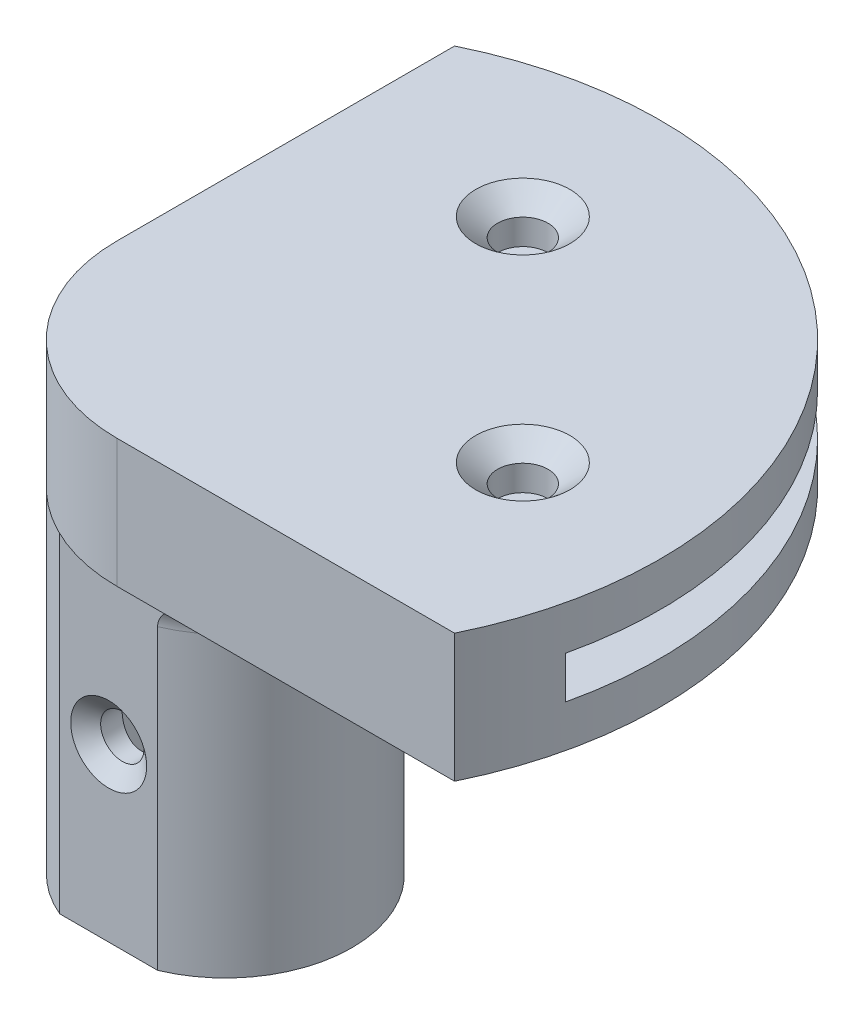
SolidWorks part; units mm, degrees
material "ABS"
ref_plane "Front Plane" through (0, 0, 0) normal (0, 0, 1) x (1, 0, 0)
ref_plane "Top Plane" through (0, 0, 0) normal (0, 1, 0) x (1, 0, 0)
ref_plane "Right Plane" through (0, 0, 0) normal (1, 0, 0) x (0, 0, -1)
sketch "Sketch2" plane through (0, 0, 0) normal (0, 1, 0) x (1, 0, 0)
  line L0 (-6.1346, -10.9507) -> (1.2352, -10.9507)
  line L1 (-6.1346, 6.6161) -> (1.2352, 6.6161)
  arc A0 (-6.1346, 6.6161) -> (-6.1346, -10.9507) centre (-2.4496, -2.1673) ccw
  circle A1 centre (-2.4496, -2.1673) radius 6.35
  arc A2 (1.2352, -10.9507) -> (1.2352, 6.6161) centre (-2.4496, -2.1673) ccw
  point P0 (-11.9404, -2.9741)
  point P1 (-9.7575, -8.2765)
  dimension "D1" = 12.7
sketch "Sketch3" plane through (0, 0, 0) normal (0, 1, 0) x (1, 0, 0)
  line L0 (0.0818, -12.8507) -> (25.4818, -12.8507)
  line L1 (-12.7876, 0.0187) -> (-12.7876, 25.4187)
  line L2 (-6.6277, -6.6908) -> (-6.6277, 27.5993)
  line L3 (-6.6277, -6.6908) -> (27.6625, -6.6908)
  line L4 (20.0088, 19.9456) -> (-9.0182, -9.0814) construction
  arc A0 (-12.7876, 0.0187) -> (0.0818, -12.8507) centre (0.0818, 0.0187) ccw
  arc A1 (25.4818, -12.8507) -> (-12.7876, 25.4187) centre (-0.2222, -0.2854) ccw
  point P0 (-9.0182, -9.0814)
  point P2 (20.0088, 19.9456)
  point P17 (-10.1818, -7.7452)
  dimension "D1" = 6.1599
extrude "Boss-Extrude1" add sketch "Sketch3" along normal blind 3.175 contours L0 A1 L1 A0
sketch "Sketch5" plane through (0, 3.175, 0) normal (0, 1, 0) x (1, 0, 0)
  line L0 (-6.6277, -6.6908) -> (-6.6277, 27.5993) construction
  line L1 (-6.6277, -6.6908) -> (27.6625, -6.6908) construction
  line L2 (0.0818, -12.8507) -> (25.4818, -12.8507)
  line L3 (-12.7876, 25.4187) -> (-12.7876, 0.0187)
  line L4 (0.0818, -12.8507) -> (25.4818, -12.8507)
  line L5 (-12.7876, 25.4187) -> (-12.7876, 0.0187)
  line L6 (-6.6277, -6.6908) -> (-6.6277, 27.5993)
  line L7 (-6.6277, -6.6908) -> (27.6625, -6.6908)
  arc A2 (25.4818, -12.8507) -> (-12.7876, 25.4187) centre (-0.2222, -0.2854) ccw
  arc A3 (-12.7876, 0.0187) -> (0.0818, -12.8507) centre (0.0818, 0.0187) ccw
  arc A4 (25.4818, -12.8507) -> (-12.7876, 25.4187) centre (-0.2222, -0.2854) ccw
  arc A5 (-12.7876, 0.0187) -> (0.0818, -12.8507) centre (0.0818, 0.0187) ccw
  dimension "D1" = 0
extrude "Boss-Extrude2" add sketch "Sketch5" along normal blind 3.175 contours L5 A5 L4 A4 L7 L6
ref_plane "Plane3" through (0, 6.35, 0) normal (0, 1, 0) x (1, 0, 0)
sketch "Sketch6" plane through (0, 6.35, 0) normal (0, 1, 0) x (1, 0, 0)
  line L0 (-12.7876, 25.4187) -> (-12.7876, 0.0187) construction
  line L1 (0.0818, -12.8507) -> (25.4818, -12.8507) construction
  line L2 (-12.7876, 25.4187) -> (-12.7876, 0.0187)
  line L3 (0.0818, -12.8507) -> (25.4818, -12.8507)
  arc A0 (-6.6277, 27.5993) -> (-12.7876, 25.4187) centre (-0.2222, -0.2854) ccw construction
  arc A1 (27.6625, -6.6908) -> (-6.6277, 27.5993) centre (-0.2222, -0.2854) ccw construction
  arc A2 (-12.7876, 0.0187) -> (0.0818, -12.8507) centre (0.0818, 0.0187) ccw construction
  arc A3 (25.4818, -12.8507) -> (27.6625, -6.6908) centre (-0.2222, -0.2854) ccw construction
  arc A4 (-6.6277, 27.5993) -> (-12.7876, 25.4187) centre (-0.2222, -0.2854) ccw
  arc A5 (27.6625, -6.6908) -> (-6.6277, 27.5993) centre (-0.2222, -0.2854) ccw
  arc A6 (-12.7876, 0.0187) -> (0.0818, -12.8507) centre (0.0818, 0.0187) ccw
  arc A7 (25.4818, -12.8507) -> (27.6625, -6.6908) centre (-0.2222, -0.2854) ccw
extrude "Boss-Extrude3" add sketch "Sketch6" along normal blind 3.302
extrude "Boss-Extrude4" add sketch "Sketch2" against normal blind 25.4
sketch "Sketch28" plane through (0, 0, 0) normal (0, -1, 0) x (-1, 0, 0)
  arc A0 (9.7575, -8.2765) -> (12.7876, 0.0187) centre (-0.0818, 0.0187) ccw construction
  point P0 (9.7575, -8.2765)
ref_plane "Plane4" through (0, 9.652, 0) normal (0, 1, 0) x (1, 0, 0)
hole_wizard "CSK for #6 Flat Head Machine Screw (100)2" positions "Sketch12" profile "Sketch11" countersink size "#6" standard "ANSI Inch"
sketch "Sketch12" plane through (0, 9.652, 0) normal (0, 1, 0) x (1, 0, 0)
  line L0 (16.9343, 0.8332) -> (16.9343, -12.8507) construction
  line L1 (0.0818, -12.8507) -> (25.4818, -12.8507) construction
  line L3 (0.8964, 16.8711) -> (-12.7876, 16.8711) construction
  line L4 (-12.7876, 25.4187) -> (-12.7876, 0.0187) construction
  line L6 (-6.6277, -6.6908) -> (20.0088, 19.9456) construction
  line L8 (0.8964, 16.8711) -> (16.9343, 0.8332) construction
  arc A1 (25.4818, -12.8507) -> (-12.7876, 25.4187) centre (-0.2222, -0.2854) ccw construction
  point P0 (16.9343, 0.8332)
  point P2 (0.8964, 16.8711)
sketch "Sketch11" plane through (16.9343, 9.652, -0.8332) normal (1, 0, 0) x (0, 0, 1)
  line L0 (0, 0) -> (0, 3.302)
  line L1 (0, 3.302) -> (1.8986, 3.302)
  line L2 (1.8986, 3.302) -> (1.8986, 1.38)
  line L3 (1.8986, 1.38) -> (3.5433, 0)
  line L5 (3.5433, 0) -> (0, 0)
  line L6 (-1.8986, 1.38) -> (-3.5433, 0) construction
  line L11 (0, -6.35) -> (0, 107.95) construction
  dimension "Thru Hole Dia." = 3.7973
  dimension "Thru Hole Depth" = 3.302
  dimension "Near C'Sink Dia." = 7.0866
  dimension "Near C'Sink Angle" = 100
ref_plane "Plane6" through (0, 0, 0) normal (0, -1, 0) x (-1, 0, 0)
sketch "Sketch20" plane through (0, 0, 0) normal (0, -1, 0) x (-1, 0, 0)
  line L2 (12.7876, 0.0187) -> (12.7876, 25.4187)
  line L3 (-25.4818, -12.8507) -> (-0.0818, -12.8507)
  line L4 (12.7876, 0.0187) -> (12.7876, 25.4187)
  line L5 (-25.4818, -12.8507) -> (-0.0818, -12.8507)
  line L8 (-1.2352, 6.6161) -> (6.1346, 6.6161)
  line L9 (-1.2352, 6.6161) -> (6.1346, 6.6161)
  line L10 (6.1346, -10.9507) -> (-1.2352, -10.9507)
  line L11 (6.1346, -10.9507) -> (-1.2352, -10.9507)
  arc A2 (12.7876, 25.4187) -> (-25.4818, -12.8507) centre (0.2222, -0.2854) ccw
  arc A3 (-0.0818, -12.8507) -> (9.5582, -8.5072) centre (-0.0818, 0.0187) ccw
  arc A4 (12.7876, 25.4187) -> (-25.4818, -12.8507) centre (0.2222, -0.2854) ccw
  arc A5 (-0.0818, -12.8507) -> (9.5582, -8.5072) centre (-0.0818, 0.0187) ccw
  arc A10 (9.7575, -8.2765) -> (6.1346, 6.6161) centre (2.4496, -2.1673) ccw
  arc A11 (9.7575, -8.2765) -> (6.1346, 6.6161) centre (2.4496, -2.1673) ccw
  arc A12 (9.7575, -8.2765) -> (12.7876, 0.0187) centre (-0.0818, 0.0187) ccw
  arc A13 (9.7575, -8.2765) -> (12.7876, 0.0187) centre (-0.0818, 0.0187) ccw
  arc A14 (6.1346, -10.9507) -> (9.5582, -8.5072) centre (2.4496, -2.1673) ccw
  arc A15 (6.1346, -10.9507) -> (9.5582, -8.5072) centre (2.4496, -2.1673) ccw
  arc A16 (-1.2352, 6.6161) -> (-1.2352, -10.9507) centre (2.4496, -2.1673) ccw
  arc A17 (-1.2352, 6.6161) -> (-1.2352, -10.9507) centre (2.4496, -2.1673) ccw
  spline S40 degree 3 poles (9.1886, 6.95) (9.1886, 13.3) (9.1886, 19.65) (9.1886, 26.0037) knots 0 0 0 0 1 1 1 1
  spline S41 degree 3 poles (9.1886, 26.0037) (2.8416, 26.0037) (-3.5069, 26.0037) (-9.8614, 26.0037) knots 1 1 1 1 2 2 2 2
  spline S42 degree 3 poles (-9.8614, 26.0037) (-9.8614, 19.655) (-9.8614, 13.3025) (-9.8614, 6.95) knots 2 2 2 2 3 3 3 3
  spline S43 degree 3 poles (-9.8614, 6.95) (-3.5147, 6.95) (2.8362, 6.95) (9.1886, 6.95) knots 3 3 3 3 4 4 4 4
  spline S45 degree 3 poles (-4.4097, 12.4089) (-4.4097, 15.1294) (-4.4097, 17.8409) (-4.4097, 20.5552) knots 11 11 11 11 12 12 12 12
  spline S47 degree 3 poles (6.4555, 12.393) (6.4555, 11.4766) (6.4555, 10.5801) (6.4555, 9.6858) knots 6 6 6 6 7 7 7 7
  spline S60 degree 3 poles (6.4543, 23.2729) (6.4543, 22.3643) (6.4543, 21.4678) (6.4543, 20.5646) knots 2 2 2 2 3 3 3 3
  spline S62 degree 3 poles (3.7419, 20.5646) (3.742, 17.8408) (3.742, 15.1169) (3.7421, 12.393) knots 4 4 4 4 5 5 5 5
  spline S64 degree 3 poles (3.7471, 23.2729) (4.6635, 23.2729) (5.56, 23.2729) (6.4543, 23.2729) knots 1 1 1 1 2 2 2 2
  spline S66 degree 3 poles (6.4543, 20.5646) (5.5414, 20.5646) (4.6417, 20.5646) (3.7419, 20.5646) knots 3 3 3 3 4 4 4 4
  spline S68 degree 3 poles (3.7471, 20.5595) (3.7471, 21.4635) (3.7471, 22.3676) (3.7471, 23.2729) knots 0 0 0 0 1 1 1 1
  spline S70 degree 3 poles (3.7472, 9.6858) (3.7472, 10.5987) (3.7472, 11.4985) (3.7472, 12.3982) knots 8 8 8 8 9 9 9 9
  spline S72 degree 3 poles (6.4555, 9.6858) (5.5468, 9.6858) (4.6504, 9.6858) (3.7472, 9.6858) knots 7 7 7 7 8 8 8 8
  spline S74 degree 3 poles (3.7421, 12.393) (4.6461, 12.393) (5.5502, 12.393) (6.4555, 12.393) knots 5 5 5 5 6 6 6 6
  spline S76 degree 3 poles (3.7472, 12.3982) (1.05, 12.3973) (-1.6473, 12.3965) (-4.3446, 12.3962) (-4.3669, 12.3962) (-4.3892, 12.4047) (-4.4097, 12.4089) knots 9 9 9 9 10 10 10 11 11 11 11
  spline S78 degree 3 poles (-4.4097, 20.5552) (-4.3738, 20.5583) (-4.3502, 20.562) (-4.3266, 20.562) (-1.6354, 20.5613) (1.0558, 20.5604) (3.7471, 20.5595) knots 12 12 12 12 13 13 13 14 14 14 14
  point P1 (5.6098, 24.2883)
  point P2 (3.7471, 23.2729)
  point P13 (3.7471, 23.2729)
  dimension "D1" = 0
extrude "Cut-Extrude7" cut sketch "Sketch20" against normal blind 2 contours S68 S66 S60 S64 | S78 S45 S76 S62 | S74 S70 S72 S47 | S41 S42 S43 S40
hole_wizard "CSK for #4 Flat Head Machine Screw (100)2" positions "Sketch26" profile "Sketch25" countersink size "#4" standard "ANSI Inch"
sketch "Sketch26" plane through (0, 0, 10.9507) normal (0, 0, 1) x (1, 0, 0)
  line L0 (-2.4497, -25.4) -> (-2.4497, 0.3858) construction
  line L1 (-6.1346, -25.4) -> (1.2352, -25.4) construction
  point P0 (-2.4497, -12.5071)
sketch "Sketch25" plane through (-2.4497, -12.5071, 10.9507) normal (1, 0, 0) x (0, -1, 0)
  line L0 (0, 0) -> (0, 10.9806)
  line L1 (0, 10.9806) -> (1.6319, 10)
  line L2 (1.6319, 10) -> (1.6319, 1.0284)
  line L3 (1.6319, 1.0284) -> (2.8575, 0)
  line L5 (2.8575, 0) -> (0, 0)
  line L6 (-1.6319, 1.0284) -> (-2.8575, 0) construction
  line L10 (0, 10.9806) -> (-1.6319, 10) construction
  line L11 (0, -6.35) -> (0, 107.95) construction
  dimension "Hole Dia." = 3.2639
  dimension "Hole Depth" = 10
  dimension "Near C'Sink Dia." = 5.715
  dimension "Near C'Sink Angle" = 100
  dimension "Drill Angle" = 118
fillet "Fillet1" radius 3 2 edges at (7.0754, 0, 2.1673)
